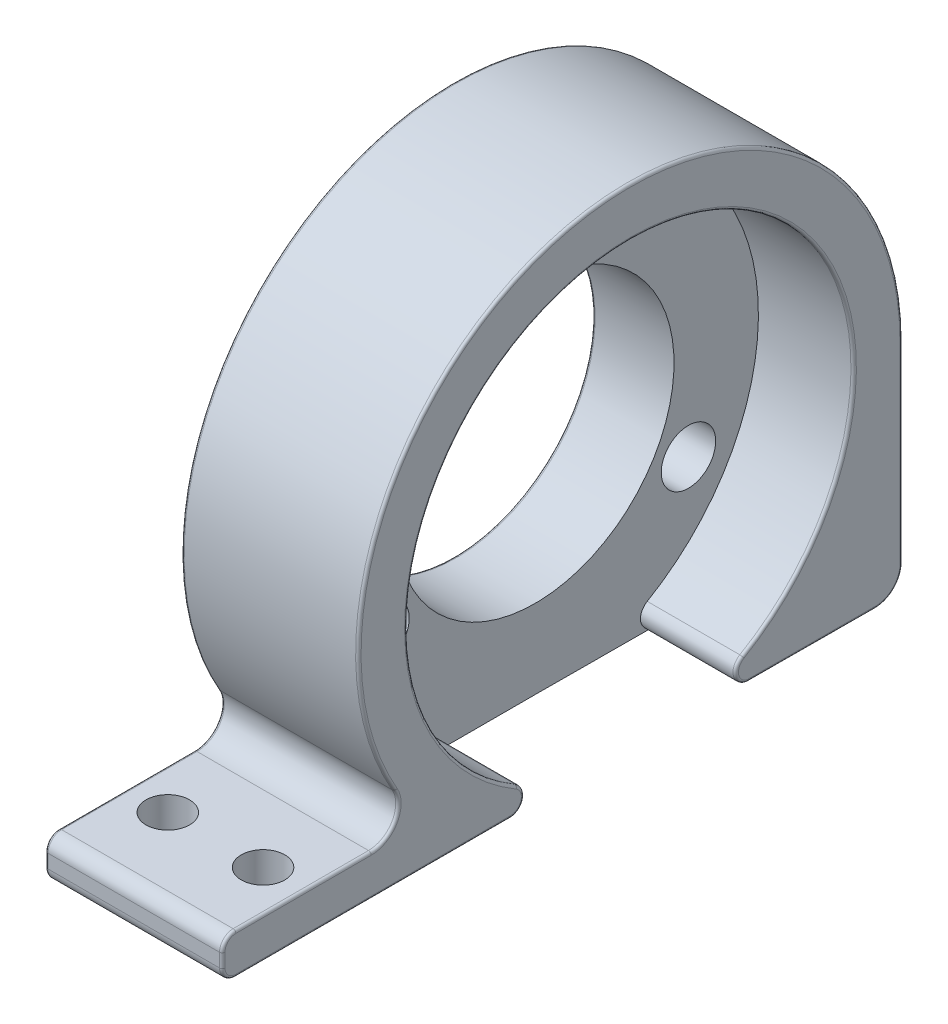
SolidWorks part; units mm, degrees
ref_plane "前视基准面" through (0, 0, 0) normal (0, 0, 1) x (1, 0, 0)
ref_plane "上视基准面" through (0, 0, 0) normal (0, 1, 0) x (1, 0, 0)
ref_plane "右视基准面" through (0, 0, 0) normal (1, 0, 0) x (0, 0, -1)
sketch "草图1" plane through (0, 0, 0) normal (1, 0, 0) x (0, 0, -1)
  line L0 (0, -8) -> (8.9958, -8.0374)
  line L1 (-15, -7) -> (-15, -7.5)
  line L2 (0, 0) -> (0, -16.0914) construction
  line L4 (-9.5263, -6.5) -> (-14.5, -6.5)
  line L5 (-14.5, -8) -> (0, -8)
  line L7 (10, 0) -> (10, -7.0374)
  arc A0 (10, -7.0374) -> (8.9958, -8.0374) centre (9, -7.0374) cw
  arc A1 (-14.5, -8) -> (-15, -7.5) centre (-14.5, -7.5) cw
  arc A2 (-15, -7) -> (-14.5, -6.5) centre (-14.5, -7) cw
  arc A4 (10, 0) -> (-8.6603, -5) centre (0, 0) ccw
  arc A7 (-8.6603, -5) -> (-9.5263, -6.5) centre (-9.5263, -5.5) cw
  circle A9 centre (0, 0) radius 5.1
  point P14 (3.9686, -6.5)
  dimension "D1" = 1
  dimension "D9" = 8
extrude "凸台-拉伸1" add sketch "草图1" along normal blind 6.5
sketch "草图7" plane through (6.5, 0, 0) normal (1, 0, 0) x (0, 0, -1)
  line L0 (-4.4091, -8) -> (4.3651, -8.0249)
  arc A0 (4.1155, -7.0924) -> (-4.1557, -7.069) centre (0, 0) ccw
  arc A1 (-4.1557, -7.069) -> (-4.4091, -8) centre (-4.4091, -7.5) cw
  arc A2 (4.1155, -7.0924) -> (4.3651, -8.0249) centre (4.3665, -7.5249) ccw
  dimension "D1" = 0.5
  dimension "D2" = 0.5
extrude "切除-拉伸4" cut sketch "草图7" against normal blind 3.5
sketch "草图5" plane through (0, -6.5, 0) normal (0, 1, 0) x (1, 0, 0)
  circle A0 centre (5, -12) radius 0.8
  circle A1 centre (1.5, -12) radius 0.8
extrude "切除-拉伸2" cut sketch "草图5" against normal up to next
fillet "圆角1" radius 0.1 24 edges at (0, -8, 7.25) (6.5, -8, 9.4545) (0, 0, -5.1) (0, 9.6593, 2.5882) (6.5, 9.6593, 2.5882) (6.5, 8.2, -0.0233) (6.5, -7.6313, 3.9266) (0, -3.5187, -10) (0, -6, 8.6603) (0, -6.5, 12.0131) (0, -6.6464, 14.8536) (0, -7.25, 15) (0, -7.8536, 14.8536) (0, -8.0187, -4.4979) (6.5, -7.8536, 14.8536) (6.5, -7.25, 15) (6.5, -6.6464, 14.8536) (6.5, -6.5, 12.0131) (6.5, -6, 8.6603) (6.5, -3.5187, -10) (6.5, -8.0276, -6.6392) (6.5, -7.6137, -3.8744) (0, -7.7459, -9.7056) (6.5, -7.7459, -9.7056)
sketch "草图6" plane through (6.5, 0, 0) normal (1, 0, 0) x (0, 0, -1)
  circle A0 centre (0, 6.5) radius 1
  circle A1 centre (5.6292, -3.25) radius 1
  circle A2 centre (-5.6292, -3.25) radius 1
  point P8 (0, 0)
  dimension "D1" = 3
extrude "切除-拉伸3" cut sketch "草图6" against normal up to next
